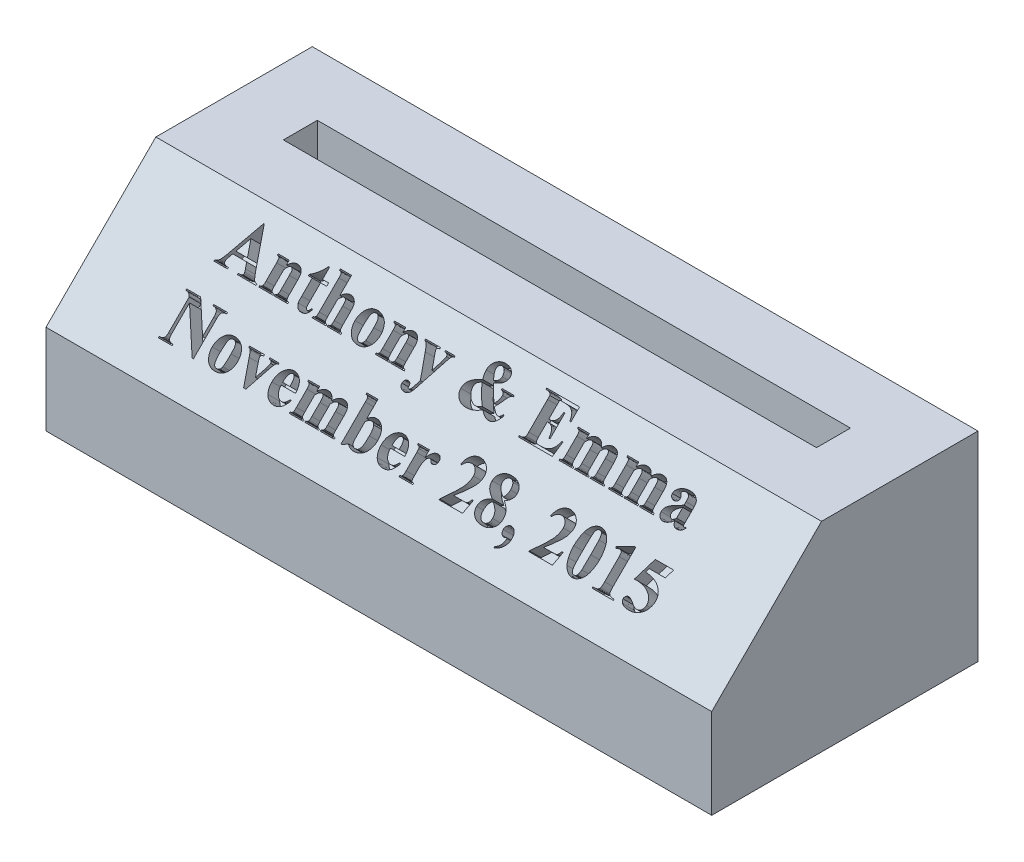
SolidWorks part; units mm, degrees
material "Copper"
ref_plane "Front Plane" through (0, 0, 0) normal (0, 0, 1) x (1, 0, 0)
ref_plane "Top Plane" through (0, 0, 0) normal (0, 1, 0) x (1, 0, 0)
ref_plane "Right Plane" through (0, 0, 0) normal (1, 0, 0) x (0, 0, -1)
sketch "Sketch2" plane through (0, 0, 0) normal (1, 0, 0) x (0, 0, -1)
  line L0 (20.955, 38.1) -> (0, 17.145)
  line L1 (0, 0) -> (50.8, 0)
  line L2 (0, 0) -> (0, 38.1)
  line L3 (0, 38.1) -> (50.8, 38.1)
  line L4 (50.8, 0) -> (50.8, 38.1)
  dimension "D1" = 45
  dimension "D2" = 50.8
  dimension "D3" = 38.1
  dimension "D4" = 20.955
extrude "Block Extrude" add sketch "Sketch2" along normal blind 127 contours L1 L4 L3 L0 L2 region at (0, 17.5063, -27.7562)
sketch "Sketch4" plane through (0, 8.5725, 8.5725) normal (0, 0.7071, 0.7071) x (1, 0, 0)
  line L0 (0, 18.4733) -> (127, 18.4733) construction
  line L1 (0, 41.7582) -> (0, 12.1233) construction
  line L2 (127, 41.7582) -> (127, 12.1233) construction
  line L3 (127, 12.1233) -> (0, 12.1233) construction
  line L4 (0, 31.1733) -> (127, 31.1733) construction
  text T0 "November 28, 2015" font "Times New Roman" height 7.62
  text T1 "Anthony & Emma" font "Times New Roman" height 7.62
  dimension "D1" = 6.35
  dimension "D2" = 12.7
extrude "Letter Cut" cut sketch "Sketch4" against normal blind 3.175
sketch "Sketch5" plane through (0, 38.1, 0) normal (0, 1, 0) x (1, 0, 0)
  line L0 (127, 35.8775) -> (0, 35.8775) construction
  line L5 (127, 20.955) -> (127, 50.8) construction
  line L6 (0, 20.955) -> (0, 50.8) construction
  line L8 (12.65, 39.116) -> (114.35, 39.116)
  line L9 (12.65, 39.116) -> (12.65, 32.639)
  line L10 (12.65, 32.639) -> (114.35, 32.639)
  line L11 (114.35, 39.116) -> (114.35, 32.639)
  line L12 (12.65, 39.116) -> (114.35, 32.639) construction
  line L13 (12.65, 32.639) -> (114.35, 39.116) construction
  point P6 (63.5, 35.8775)
  dimension "D1" = 6.477
  dimension "D2" = 101.7
extrude "Glass Cut" cut sketch "Sketch5" against normal blind 19.05
